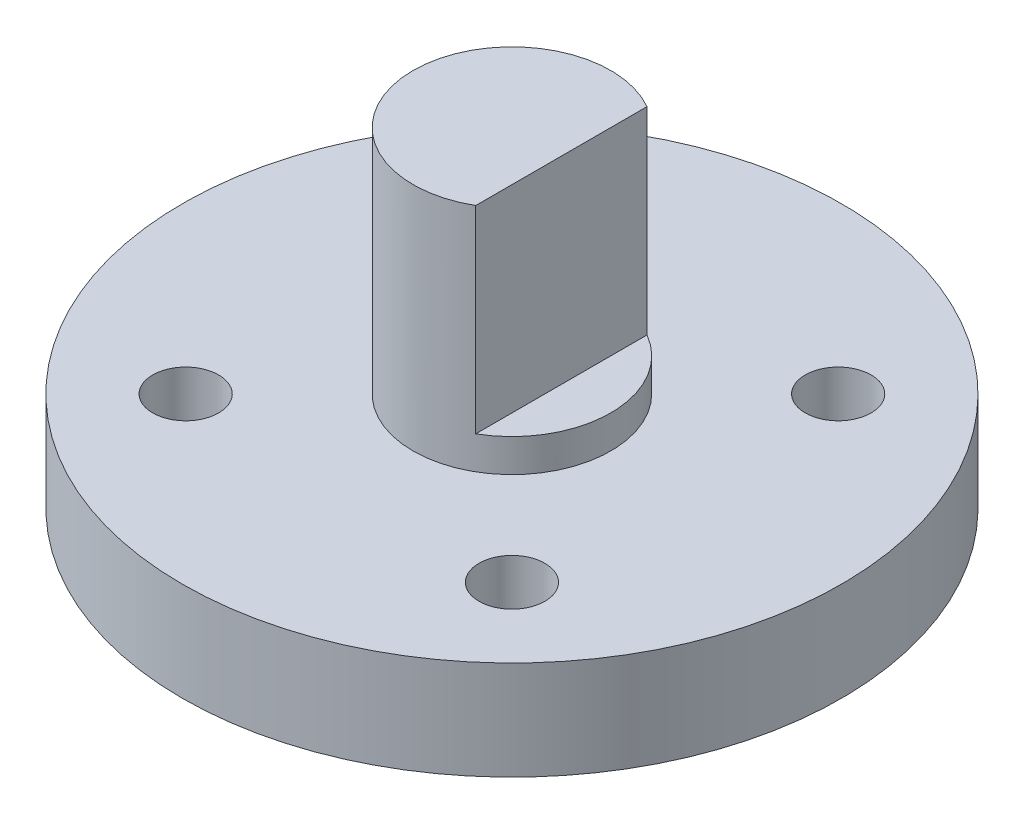
SolidWorks part; units mm, degrees
ref_plane "Alzado" through (0, 0, 0) normal (0, 0, 1) x (1, 0, 0)
ref_plane "Planta" through (0, 0, 0) normal (0, 1, 0) x (1, 0, 0)
ref_plane "Vista lateral" through (0, 0, 0) normal (1, 0, 0) x (0, 0, -1)
sketch "Croquis1" plane through (0, 0, 0) normal (0, 1, 0) x (1, 0, 0)
  line L0 (0, 0) -> (-6.6149, 6.6149) construction
  line L1 (-6.6149, 6.6149) -> (7.3418, -7.3418) construction
  line L2 (0, 0) -> (-6.786, -6.786) construction
  line L3 (-6.786, -6.786) -> (7.1299, 7.1299) construction
  circle A0 centre (0, 0) radius 10
  circle A1 centre (-4.9497, 4.9497) radius 1
  circle A5 centre (0, 0) radius 3
  circle A7 centre (4.9497, 4.9497) radius 1
  circle A8 centre (4.9497, -4.9497) radius 1
  circle A9 centre (-4.9497, -4.9497) radius 1
  point P14 (-1.6569, -4)
  point P23 (0, 0)
  dimension "D1" = 20
  dimension "D2" = 2
  dimension "D4" = 7
  dimension "D5" = 6
  dimension "D7" = 45
  dimension "D3" = 4
extrude "Saliente-Extruir1" add sketch "Croquis1" along normal blind 3 contours A0 A1 | A5 | A5 region at (-9.7172, 0, 0) region at (0, 0, 0)
extrude "Saliente-Extruir2" add sketch "Croquis1<3>" along normal blind 7 from surface contours A5 starting at face at (-4.9497, 3, 5.9497)
sketch "Croquis1<3>" plane through (0, 0, 0) normal (0, 1, 0) x (1, 0, 0) same geometry as "Croquis1"
sketch "Croquis2" plane through (0, 10, 0) normal (0, 1, 0) x (1, 0, 0)
  line L0 (1.5, 2.5981) -> (1.5, -2.5981)
  circle A0 centre (0, 0) radius 3 construction
  arc A1 (1.5, -2.5981) -> (1.5, 2.5981) centre (0, 0) ccw
  dimension "D1" = 1.5
extrude "Cortar-Extruir1" cut sketch "Croquis2" against normal blind 6
